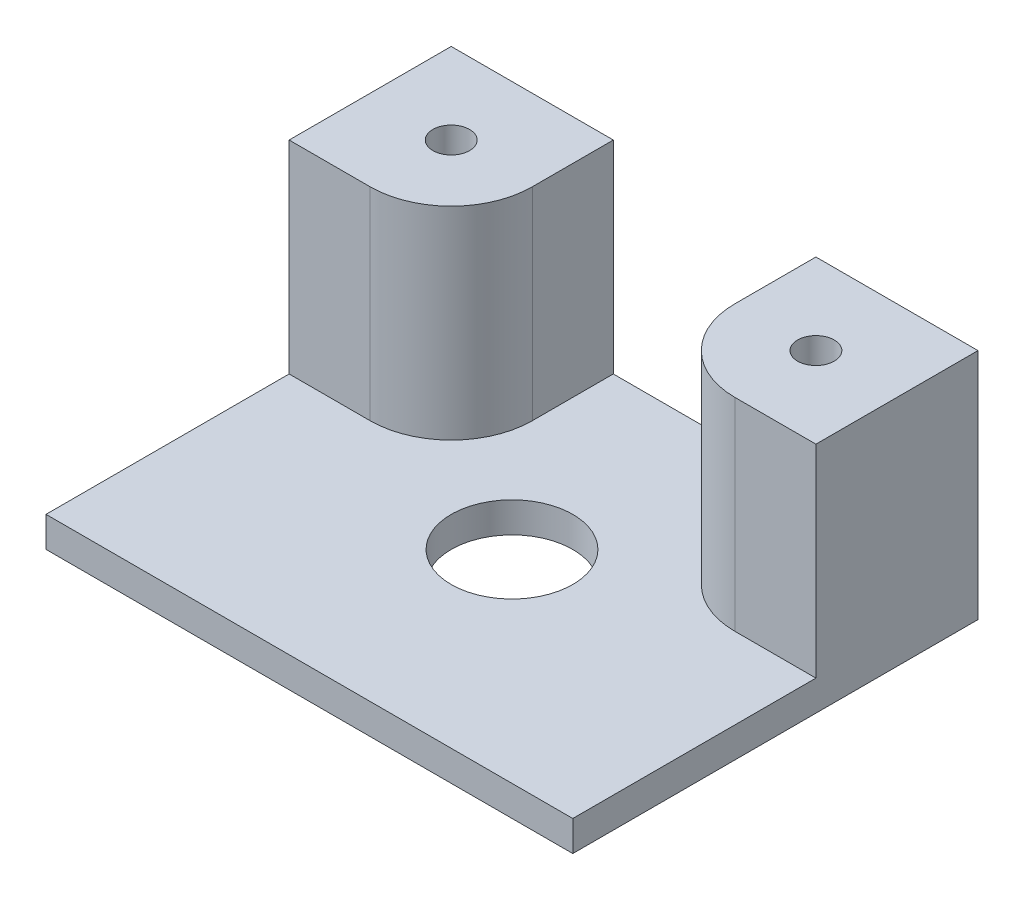
SolidWorks part; units mm, degrees
material "AISI 1020"
ref_plane "Front Plane" through (0, 0, 0) normal (0, 0, 1) x (1, 0, 0)
ref_plane "Top Plane" through (0, 0, 0) normal (0, 1, 0) x (1, 0, 0)
ref_plane "Right Plane" through (0, 0, 0) normal (1, 0, 0) x (0, 0, -1)
sketch "Sketch1" plane through (0, 0, 0) normal (0, 1, 0) x (1, 0, 0)
  line L1 (0, 0) -> (165.1, 0)
  line L2 (0, 0) -> (0, 127)
  line L3 (0, 127) -> (165.1, 127)
  line L4 (165.1, 0) -> (165.1, 127)
  dimension "D1" = 165.1
  dimension "D2" = 127
extrude "Boss-Extrude1" add sketch "Sketch1" along normal blind 9.525
sketch "Sketch2" plane through (0, 9.525, 0) normal (0, 1, 0) x (1, 0, 0)
  line L1 (165.1, 127) -> (0, 127) construction
  line L3 (165.1, 0) -> (165.1, 127) construction
  circle A0 centre (82.55, 63.5) radius 19.05
  dimension "D3" = 38.1
  dimension "D1" = 63.5
  dimension "D2" = 82.55
extrude "Cut-Extrude1" cut sketch "Sketch2" against normal through all
sketch "Sketch3" plane through (0, 9.525, 0) normal (0, 1, 0) x (1, 0, 0)
  line L0 (0, 101.6) -> (50.8, 101.6) construction
  line L1 (0, 127) -> (50.8, 127)
  line L2 (0, 127) -> (0, 76.2)
  line L3 (0, 76.2) -> (25.4, 76.2)
  line L4 (50.8, 127) -> (50.8, 101.6)
  line L5 (165.1, 127) -> (114.3, 127)
  line L6 (165.1, 127) -> (165.1, 76.2)
  line L7 (165.1, 76.2) -> (139.7, 76.2)
  line L8 (114.3, 127) -> (114.3, 101.6)
  line L9 (114.3, 101.6) -> (165.1, 101.6) construction
  arc A0 (50.8, 101.6) -> (25.4, 76.2) centre (25.4, 101.6) cw
  arc A1 (114.3, 101.6) -> (139.7, 76.2) centre (139.7, 101.6) ccw
  dimension "D1" = 50.8
  dimension "D2" = 50.8
  dimension "D3" = 50.8
  dimension "D4" = 50.8
extrude "Boss-Extrude3" add sketch "Sketch3" along normal blind 63.5
hole_wizard "1/2-20 Tapped Hole1" positions "3DSketch2" profile "Sketch6" tap size "1/2-20" standard "ANSI Inch"
sketch3d "3DSketch2"
  line L1 (25.4, 73.025, -101.6) -> (25.4, 73.025, -127) construction
  line L2 (50.8, 73.025, -127) -> (0, 73.025, -127) construction
  line L4 (139.7, 73.025, -101.6) -> (139.7, 73.025, -127) construction
  line L5 (165.1, 73.025, -127) -> (114.3, 73.025, -127) construction
  point P0 (25.4, 73.025, -101.6)
  point P2 (139.7, 73.025, -101.6)
  dimension "D1" = 25.4
  dimension "D2" = 25.4
sketch "Sketch6" plane through (25.4, 73.025, -101.6) normal (1, 0, 0) x (0, 0, 1)
  line L0 (0, 0) -> (0, 35.2076)
  line L1 (0, 35.2076) -> (5.7544, 31.75)
  line L2 (5.7544, 31.75) -> (5.7544, 0)
  line L5 (5.7544, 0) -> (0, 0)
  line L10 (0, 35.2076) -> (-5.7544, 31.75) construction
  line L11 (0, -6.35) -> (0, 107.95) construction
  dimension "Tap Drill Dia." = 11.5087
  dimension "Tap Drill Depth" = 31.75
  dimension "Drill Angle" = 118
cosmetic thread "Hole Thread2"
cosmetic thread "Hole Thread3"
